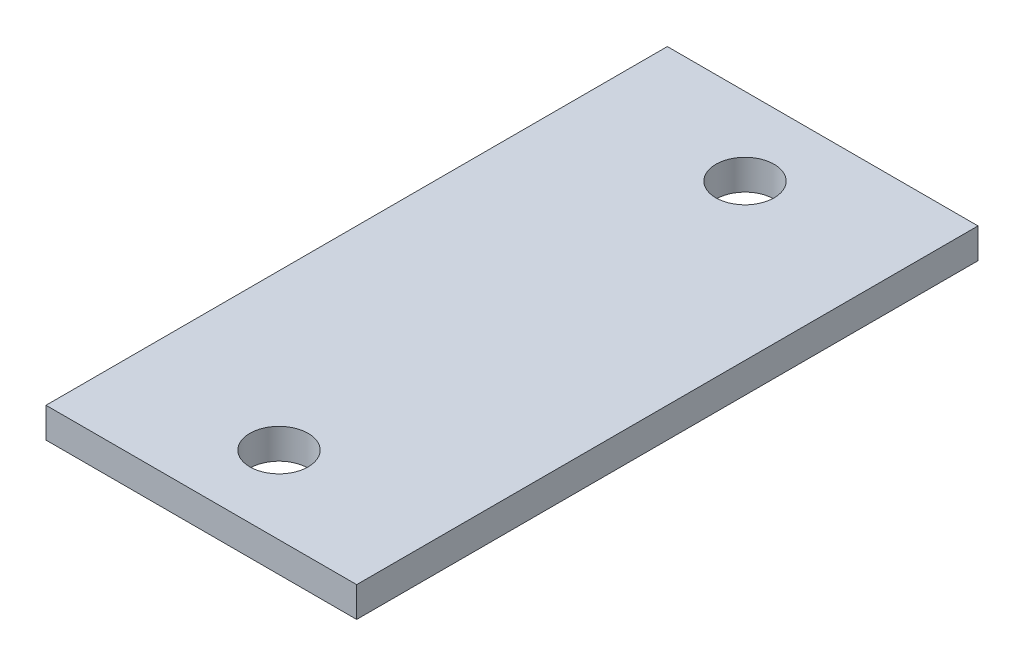
SolidWorks part; units mm, degrees
material "Plain Carbon Steel"
ref_plane "Front Plane" through (0, 0, 0) normal (0, 0, 1) x (1, 0, 0)
ref_plane "Top Plane" through (0, 0, 0) normal (0, 1, 0) x (1, 0, 0)
ref_plane "Right Plane" through (0, 0, 0) normal (1, 0, 0) x (0, 0, -1)
sketch "Sketch1" plane through (0, 0, 0) normal (0, 1, 0) x (1, 0, 0)
  line L1 (0, 0) -> (50.8, 0)
  line L2 (0, 0) -> (0, 101.6)
  line L3 (0, 101.6) -> (50.8, 101.6)
  line L4 (50.8, 0) -> (50.8, 101.6)
  line L8 (0, 12.7) -> (50.8, 12.7) construction
  line L9 (138.2933, -166.1483) -> (138.2933, -83.5983) construction
  circle A0 centre (25.4, 12.7) radius 4.7625
  circle A1 centre (25.4, 88.9) radius 4.7625
  circle A2 centre (138.2933, -166.1483) radius 101.6 construction
  circle A3 centre (138.2933, -83.5983) radius 4.7625 construction
  dimension "D6" = 9.525
  dimension "D4" = 203.2
  dimension "D9" = 9.525
  dimension "D1" = 101.6
  dimension "D2" = 88.9
  dimension "D3" = 25.4
  dimension "D5" = 50.8
  dimension "D7" = 88.9
  dimension "D8" = 82.55
extrude "Hammer" add sketch "Sketch1" along normal blind 4.9352
